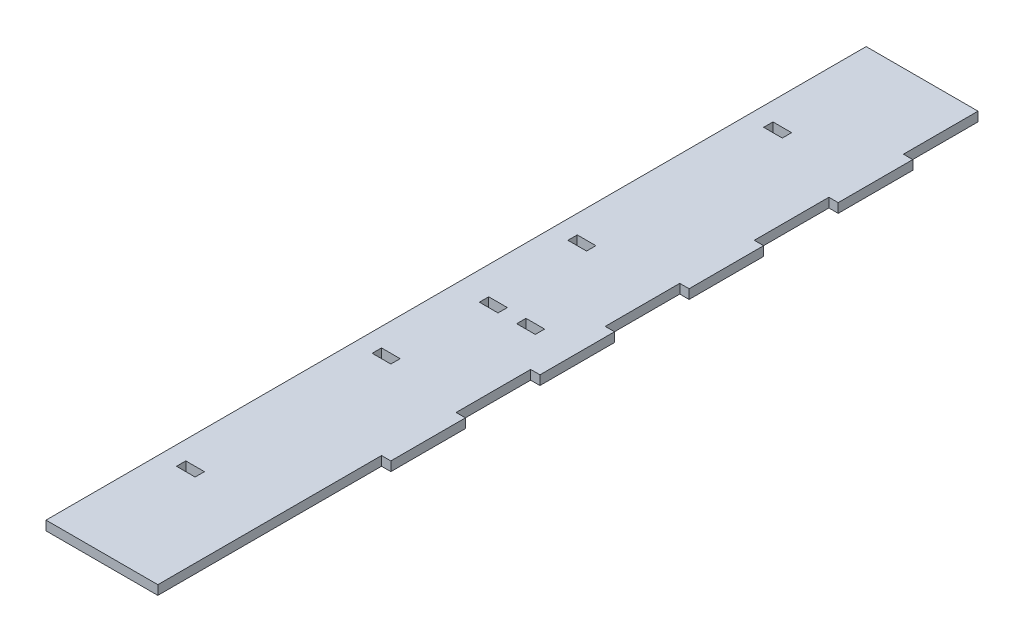
SolidWorks part; units mm, degrees
ref_plane "Front Plane" through (0, 0, 0) normal (0, 0, 1) x (1, 0, 0)
ref_plane "Top Plane" through (0, 0, 0) normal (0, 1, 0) x (1, 0, 0)
ref_plane "Right Plane" through (0, 0, 0) normal (1, 0, 0) x (0, 0, -1)
sketch "Sketch1" plane through (0, 0, 0) normal (0, 0, 1) x (1, 0, 0)
  line L1 (38.1, 38.1) -> (-38.1, 38.1)
  line L2 (38.1, 38.1) -> (38.1, 44.45)
  line L3 (38.1, 44.45) -> (-38.1, 44.45)
  line L4 (-38.1, 38.1) -> (-38.1, 44.45)
  dimension "D1" = 6.35
extrude "Boss-Extrude1" add sketch "Sketch1" along normal blind 558.8
sketch "Sketch2" plane through (0, 44.45, 0) normal (0, 1, 0) x (1, 0, 0)
  line L0 (0, -558.8) -> (0, 0) construction
  line L1 (38.1, -558.8) -> (-38.1, -558.8) construction
  line L2 (0, -279.4) -> (-28.148, -279.4) construction
  line L4 (19.05, -282.575) -> (6.35, -282.575)
  line L5 (19.05, -282.575) -> (19.05, -276.225)
  line L6 (19.05, -276.225) -> (6.35, -276.225)
  line L7 (6.35, -282.575) -> (6.35, -276.225)
  line L8 (-6.35, -282.575) -> (-19.05, -282.575)
  line L9 (-6.35, -282.575) -> (-6.35, -276.225)
  line L10 (-6.35, -276.225) -> (-19.05, -276.225)
  line L11 (-19.05, -282.575) -> (-19.05, -276.225)
  dimension "D1" = 6.35
  dimension "D2" = 6.35
  dimension "D3" = 12.7
  dimension "D4" = 12.7
  dimension "D5" = 12.7
extrude "Cut-Extrude1" cut sketch "Sketch2" against normal through all
sketch "Sketch3" plane through (38.1, 0, 0) normal (1, 0, 0) x (0, 0, -1)
  line L0 (-558.8, 38.1) -> (0, 38.1) construction
  line L1 (-406.4, 38.1) -> (-355.6, 38.1)
  line L2 (-406.4, 38.1) -> (-406.4, 44.45)
  line L3 (-406.4, 44.45) -> (-355.6, 44.45)
  line L4 (-355.6, 38.1) -> (-355.6, 44.45)
  line L5 (-558.8, 44.45) -> (0, 44.45) construction
  line L6 (-355.6, 38.1) -> (-355.6, 44.45) construction
  line L7 (-406.4, 44.45) -> (-406.4, 38.1) construction
  line L8 (-304.8, 44.45) -> (-304.8, 38.1) construction
  line L9 (-304.8, 44.45) -> (-254, 44.45)
  line L10 (-304.8, 44.45) -> (-304.8, 38.1)
  line L11 (-304.8, 38.1) -> (-254, 38.1)
  line L12 (-254, 44.45) -> (-254, 38.1)
  line L13 (-203.2, 44.45) -> (-203.2, 38.1) construction
  line L14 (-203.2, 44.45) -> (-152.4, 44.45)
  line L15 (-203.2, 44.45) -> (-203.2, 38.1)
  line L16 (-203.2, 38.1) -> (-152.4, 38.1)
  line L17 (-152.4, 44.45) -> (-152.4, 38.1)
  line L18 (-101.6, 44.45) -> (-101.6, 38.1) construction
  line L19 (-101.6, 44.45) -> (-50.8, 44.45)
  line L20 (-101.6, 44.45) -> (-101.6, 38.1)
  line L21 (-101.6, 38.1) -> (-50.8, 38.1)
  line L22 (-50.8, 44.45) -> (-50.8, 38.1)
  line L23 (-254, 38.1) -> (-254, 44.45) construction
  line L24 (-152.4, 38.1) -> (-152.4, 44.45) construction
  line L25 (-101.6, 38.1) -> (-50.8, 38.1) construction
  line L26 (-50.8, 38.1) -> (-50.8, 44.45) construction
extrude "Boss-Extrude2" add sketch "Sketch3" along normal up to surface (6.35 mm away)
sketch "Sketch4" plane through (0, 44.45, 0) normal (0, 1, 0) x (1, 0, 0)
  line L0 (-38.1, -558.8) -> (-38.1, 0) construction
  line L1 (-12.7, -482.6) -> (-25.4, -482.6)
  line L2 (-12.7, -482.6) -> (-12.7, -476.25)
  line L3 (-12.7, -476.25) -> (-25.4, -476.25)
  line L4 (-25.4, -482.6) -> (-25.4, -476.25)
  line L5 (38.1, -558.8) -> (-38.1, -558.8) construction
  dimension "D1" = 6.35
  dimension "D2" = 12.7
  dimension "D3" = 12.7
  dimension "D4" = 76.2
extrude "Cut-Extrude2" cut sketch "Sketch4" against normal through all
pattern_linear "LPattern1" count 4 spacing 133.35 along (0, 0, -1) of "Cut-Extrude2"
